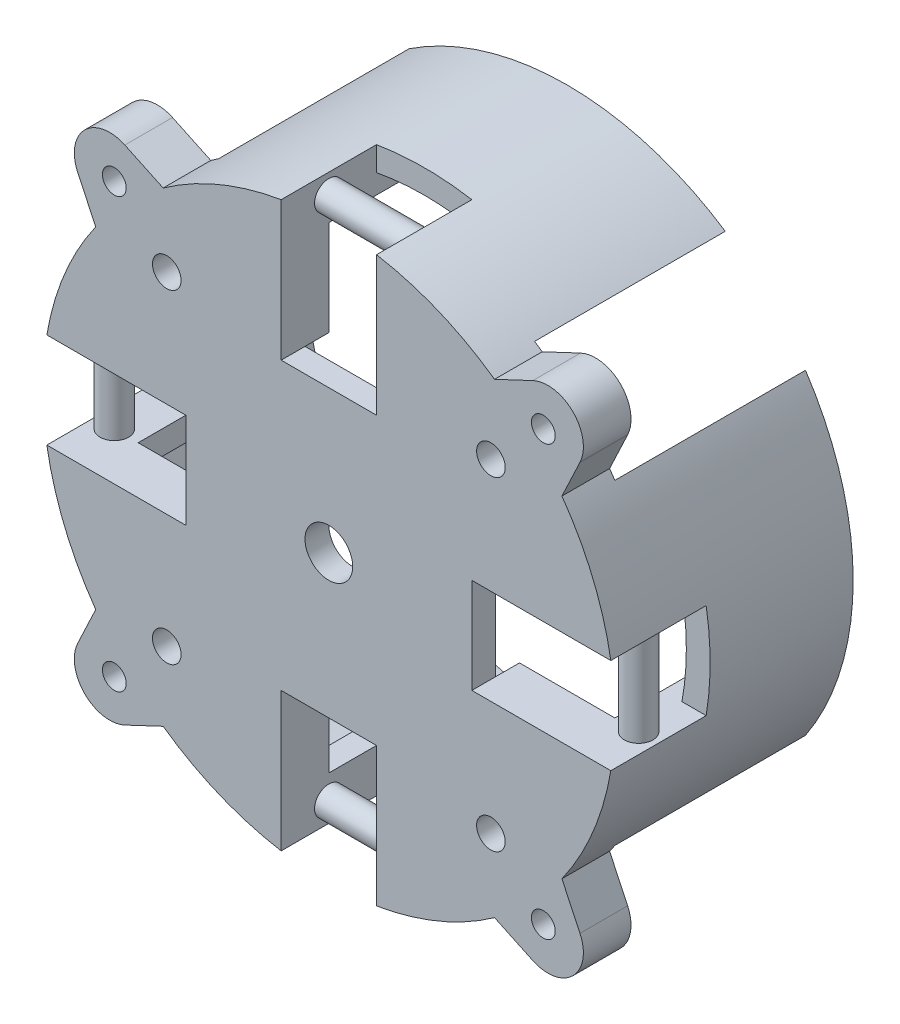
SolidWorks part; units mm, degrees
material "ABS"
ref_plane "前视基准面" through (0, 0, 0) normal (0, 0, 1) x (1, 0, 0)
ref_plane "上视基准面" through (0, 0, 0) normal (0, 1, 0) x (1, 0, 0)
ref_plane "右视基准面" through (0, 0, 0) normal (1, 0, 0) x (0, 0, -1)
sketch "草图1" plane through (0, 0, 0) normal (0, 0, 1) x (1, 0, 0)
  circle A0 centre (0, 0) radius 60
  dimension "D1" = 120
extrude "凸台-拉伸1" add sketch "草图1" against normal blind 50
sketch "草图2" plane through (0, 0, 0) normal (0, 0, 1) x (1, 0, 0)
  line L0 (0, 30) -> (0, 0) construction
  line L1 (0, 0) -> (0, -30) construction
  line L2 (-30, 0) -> (0, 0) construction
  line L3 (0, 0) -> (30, 0) construction
  circle A4 centre (34, 34) radius 3
  circle A5 centre (34, -34) radius 3
  circle A6 centre (-34, -34) radius 3
  circle A7 centre (-34, 34) radius 3
  dimension "D1" = 68
  dimension "D2" = 68
  dimension "D3" = 6
  dimension "D4" = 6
  dimension "D9" = 6
  dimension "D10" = 6
  dimension "D5" = 30
  dimension "D6" = 30
  dimension "D7" = 30
  dimension "D8" = 30
extrude "切除-拉伸1" cut sketch "草图2" against normal blind 10
shell "抽壳1" thickness 5 removed face at (60, 0, -50)
sketch "草图3" plane through (0, 0, 0) normal (0, 0, 1) x (1, 0, 0)
  line L1 (21.65, 21.65) -> (-21.65, 21.65)
  line L2 (21.65, 21.65) -> (21.65, -21.65)
  line L3 (21.65, -21.65) -> (-21.65, -21.65)
  line L4 (-21.65, 21.65) -> (-21.65, -21.65)
  line L5 (21.65, 21.65) -> (-21.65, -21.65) construction
  line L6 (21.65, -21.65) -> (-21.65, 21.65) construction
  line L7 (22.5, 22.5) -> (-22.5, 22.5)
  line L8 (22.5, 22.5) -> (22.5, -22.5)
  line L9 (22.5, -22.5) -> (-22.5, -22.5)
  line L10 (-22.5, 22.5) -> (-22.5, -22.5)
  line L11 (22.5, 22.5) -> (-22.5, -22.5) construction
  line L12 (22.5, -22.5) -> (-22.5, 22.5) construction
  point P0 (0, 0)
  point P7 (0, 0)
  dimension "D1" = 43.3
  dimension "D2" = 43.3
  dimension "D3" = 45
  dimension "D4" = 45
extrude "凸台-拉伸2" add sketch "草图3" against normal blind 25
sketch "草图4" plane through (0, 0, -5) normal (0, 0, -1) x (-1, 0, 0)
  circle A0 centre (0, 0) radius 5
  dimension "D1" = 10
extrude "切除-拉伸2" cut sketch "草图4" against normal through all
sketch "草图5" plane through (0, 0, 0) normal (0, 0, 1) x (1, 0, 0)
  line L0 (0, -45) -> (0, 0) construction
  line L1 (-60, -10) -> (-30, -10)
  line L2 (-60, -10) -> (-60, 10)
  line L3 (-60, 10) -> (-30, 10)
  line L4 (-30, -10) -> (-30, 10)
  line L5 (-60, -10) -> (-30, 10) construction
  line L6 (-60, 10) -> (-30, -10) construction
  line L7 (10, 30) -> (-10, 30)
  line L8 (10, 30) -> (10, 60)
  line L9 (10, 60) -> (-10, 60)
  line L10 (-10, 30) -> (-10, 60)
  line L11 (10, 30) -> (-10, 60) construction
  line L12 (10, 60) -> (-10, 30) construction
  line L13 (30, 10) -> (60, 10)
  line L14 (30, 10) -> (30, -10)
  line L15 (30, -10) -> (60, -10)
  line L16 (60, 10) -> (60, -10)
  line L17 (30, 10) -> (60, -10) construction
  line L18 (30, -10) -> (60, 10) construction
  line L19 (10, -30) -> (-10, -30)
  line L20 (10, -30) -> (10, -60)
  line L21 (10, -60) -> (-10, -60)
  line L22 (-10, -30) -> (-10, -60)
  line L23 (10, -30) -> (-10, -60) construction
  line L24 (10, -60) -> (-10, -30) construction
  line L25 (0, 0) -> (0, 45) construction
  line L26 (45, 0) -> (0, 0) construction
  line L27 (0, 0) -> (-45, 0) construction
  point P0 (-45, 0)
  point P5 (0, 45)
  point P10 (45, 0)
  point P15 (0, -45)
  dimension "D1" = 30
  dimension "D2" = 30
  dimension "D3" = 30
  dimension "D4" = 30
  dimension "D5" = 20
  dimension "D6" = 20
  dimension "D7" = 20
  dimension "D8" = 20
  dimension "D9" = 30
  dimension "D10" = 30
  dimension "D11" = 30
  dimension "D12" = 30
extrude "切除-拉伸3" cut sketch "草图5" against normal blind 20
sketch "草图6" plane through (0, 0, -5) normal (0, 0, -1) x (-1, 0, 0)
  line L0 (-30, 10) -> (-30, -10) construction
  line L1 (-54.0833, 10) -> (-30, 10)
  line L2 (-54.0833, 10) -> (-54.0833, 15)
  line L3 (-54.0833, 15) -> (-30, 15)
  line L4 (-30, 10) -> (-30, 15)
  line L5 (-54.0833, -10) -> (-30, -10)
  line L6 (-54.0833, -10) -> (-54.0833, -15)
  line L7 (-54.0833, -15) -> (-30, -15)
  line L8 (-30, -10) -> (-30, -15)
  line L9 (10, 54.0833) -> (10, 30)
  line L10 (10, 54.0833) -> (15, 54.0833)
  line L11 (15, 54.0833) -> (15, 30)
  line L12 (10, 30) -> (15, 30)
  line L13 (-10, 54.0833) -> (-10, 30)
  line L14 (-10, 54.0833) -> (-15, 54.0833)
  line L15 (-15, 54.0833) -> (-15, 30)
  line L16 (-10, 30) -> (-15, 30)
  line L17 (54.0833, -10) -> (30, -10)
  line L18 (54.0833, -10) -> (54.0833, -15)
  line L19 (54.0833, -15) -> (30, -15)
  line L20 (30, -10) -> (30, -15)
  line L21 (54.0833, 10) -> (30, 10)
  line L22 (54.0833, 10) -> (54.0833, 15)
  line L23 (54.0833, 15) -> (30, 15)
  line L24 (30, 10) -> (30, 15)
  line L25 (-10, -54.0833) -> (-10, -30)
  line L26 (-10, -54.0833) -> (-15, -54.0833)
  line L27 (-15, -54.0833) -> (-15, -30)
  line L28 (-10, -30) -> (-15, -30)
  line L29 (10, -54.0833) -> (10, -30)
  line L30 (10, -54.0833) -> (15, -54.0833)
  line L31 (15, -54.0833) -> (15, -30)
  line L32 (10, -30) -> (15, -30)
  dimension "D1" = 5
  dimension "D2" = 5
  dimension "D3" = 4
extrude "凸台-拉伸3" add sketch "草图6" along normal blind 20
sketch "草图7" plane through (10, 0, 0) normal (-1, 0, 0) x (0, 0, 1)
  line L0 (0, 0) -> (-83.2029, 0) construction
  line L1 (-10, 55) -> (-10, -55) construction
  line L2 (0, 30) -> (0, 59.1608) construction
  circle A0 centre (-10, 55) radius 3
  circle A1 centre (-10, -55) radius 3
  dimension "D2" = 6
  dimension "D3" = 6
  dimension "D1" = 110
  dimension "D4" = 10
extrude "凸台-拉伸4" add sketch "草图7" along normal up to surface (20 mm away) up to face at (-10, 45.2126, -13.5714)
sketch "草图8" plane through (0, 10, 0) normal (0, -1, 0) x (1, 0, 0)
  line L0 (55, -10) -> (-55, -10) construction
  line L1 (0, 0) -> (0, 55.0435) construction
  circle A0 centre (55, -10) radius 3
  circle A1 centre (-55, -10) radius 3
  dimension "D3" = 6
  dimension "D4" = 6
  dimension "D1" = 10
  dimension "D2" = 110
extrude "凸台-拉伸5" add sketch "草图8" along normal up to next
sketch "草图9" plane through (0, 0, -15) normal (0, 0, -1) x (-1, 0, 0)
  circle A0 centre (-34, -34) radius 2.5
  circle A1 centre (-34, 34) radius 2.5
  circle A2 centre (34, -34) radius 2.5
  circle A3 centre (34, 34) radius 2.5
  dimension "D1" = 5
  dimension "D2" = 5
  dimension "D3" = 5
  dimension "D4" = 5
sketch "草图10" plane through (0, 0, 0) normal (0, 0, 1) x (1, 0, 0)
  line L0 (0, 0) -> (-45.9619, 45.9619) construction
  line L1 (0, 0) -> (0, 30) construction
  line L2 (-10, 30) -> (10, 30) construction
  line L3 (0, 0) -> (30, 0) construction
  line L4 (30, 10) -> (30, -10) construction
  line L5 (-48.9041, 34.7619) -> (-52.6894, 42.7899)
  line L6 (-45.9619, 45.9619) -> (-52.6894, 42.7899) construction
  line L7 (-45.9619, 45.9619) -> (-55.826, 55.826) construction
  line L8 (-34.7619, 48.9041) -> (-42.7899, 52.6894)
  line L9 (45.9619, 45.9619) -> (55.826, 55.826) construction
  line L10 (45.9619, 45.9619) -> (52.6894, 42.7899) construction
  line L11 (34.7619, 48.9041) -> (42.7899, 52.6894)
  line L12 (48.9041, 34.7619) -> (52.6894, 42.7899)
  line L13 (45.9619, -45.9619) -> (52.6894, -42.7899) construction
  line L14 (45.9619, -45.9619) -> (55.826, -55.826) construction
  line L15 (-45.9619, -45.9619) -> (-55.826, -55.826) construction
  line L16 (-45.9619, -45.9619) -> (-52.6894, -42.7899) construction
  line L17 (48.9041, -34.7619) -> (52.6894, -42.7899)
  line L18 (34.7619, -48.9041) -> (42.7899, -52.6894)
  line L19 (-34.7619, -48.9041) -> (-42.7899, -52.6894)
  line L20 (-48.9041, -34.7619) -> (-52.6894, -42.7899)
  arc A0 (-10, 59.1608) -> (-59.1608, 10) centre (0, 0) ccw construction
  arc A1 (-52.6894, 42.7899) -> (-42.7899, 52.6894) centre (-45.9619, 45.9619) cw
  arc A2 (-48.9041, 34.7619) -> (-34.7619, 48.9041) centre (0, 0) cw
  circle A3 centre (-45, 45) radius 2.5
  circle A4 centre (45, 45) radius 2.5
  arc A5 (48.9041, 34.7619) -> (34.7619, 48.9041) centre (0, 0) ccw
  arc A6 (52.6894, 42.7899) -> (42.7899, 52.6894) centre (45.9619, 45.9619) ccw
  arc A7 (52.6894, -42.7899) -> (42.7899, -52.6894) centre (45.9619, -45.9619) cw
  arc A8 (48.9041, -34.7619) -> (34.7619, -48.9041) centre (0, 0) cw
  circle A9 centre (45, -45) radius 2.5
  circle A10 centre (-45, -45) radius 2.5
  arc A11 (-48.9041, -34.7619) -> (-34.7619, -48.9041) centre (0, 0) ccw
  arc A12 (-52.6894, -42.7899) -> (-42.7899, -52.6894) centre (-45.9619, -45.9619) ccw
  dimension "D6" = 5
  dimension "D1" = 45
  dimension "D2" = 10
  dimension "D3" = 7
  dimension "D4" = 65
  dimension "D5" = 45
extrude "凸台-拉伸6" add sketch "草图10" against normal blind 10
sketch "草图11" plane through (0, 0, -50) normal (0, 0, -1) x (-1, 0, 0)
  line L1 (-50, 50) -> (50, 50)
  line L2 (-50, 50) -> (-50, -50)
  line L3 (-50, -50) -> (50, -50)
  line L4 (50, 50) -> (50, -50)
  line L5 (-50, 50) -> (50, -50) construction
  line L6 (-50, -50) -> (50, 50) construction
  point P0 (0, 0)
  dimension "D1" = 100
  dimension "D2" = 100
extrude "切除-拉伸4" cut sketch "草图11" against normal up to surface (40 mm away) up to face at (-47.5, -45, -10)
